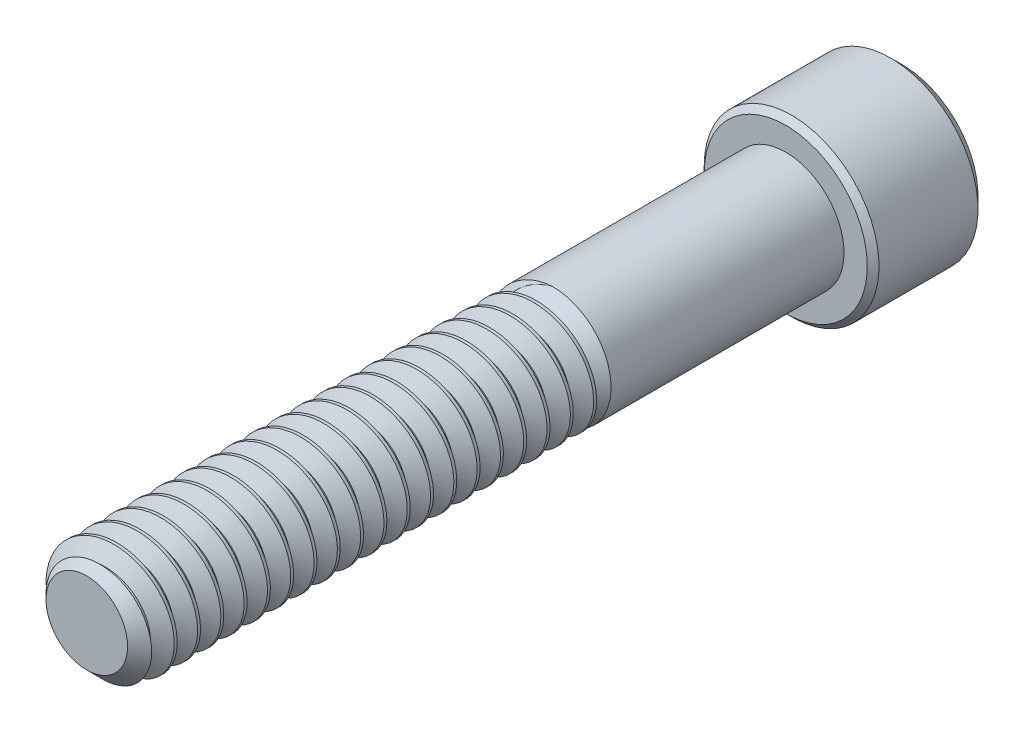
SolidWorks part; units mm, degrees
material "Cast Alloy Steel"
ref_plane "Front Plane" through (0, 0, 0) normal (0, 0, 1) x (1, 0, 0)
ref_plane "Top Plane" through (0, 0, 0) normal (0, 1, 0) x (1, 0, 0)
ref_plane "Right Plane" through (0, 0, 0) normal (1, 0, 0) x (0, 0, -1)
sketch "Sketch1" plane through (0, 0, 0) normal (0, 0, 1) x (1, 0, 0)
  line L0 (0, 3.175) -> (0, -3.175) construction
  circle A0 centre (0, 0) radius 3.175
  dimension "OD" = 6.35
extrude "Extrude1" add sketch "Sketch1" against normal blind 38.1
sketch "Sketch2" plane through (0, 0, 0) normal (0, 0, 1) x (1, 0, 0)
  circle A0 centre (0, 0) radius 3.175 construction
  circle A1 centre (0, 0) radius 3.175
curve "Helix/Spiral1" pitch 1.27 height 27.94 turns 22 parameters "pitch"=1.27
chamfer "Chamfer3" distance 0.9525 angle 45 1 edges at (3.175, 0, 0)
sketch "Sketch3" plane through (0, 0, 0) normal (1, 0, 0) x (0, 0, -1)
  line L0 (-1.1112, 3.175) -> (-0.635, 2.3501)
  line L1 (-0.635, 2.3501) -> (-0.4763, 2.3501)
  line L2 (-0.4763, 2.3501) -> (0, 3.175)
  line L3 (-1.1112, 3.175) -> (0, 3.175)
  line L4 (-0.5556, 3.175) -> (-0.5556, 2.3501) construction
  line L5 (-0.8731, 2.7626) -> (-0.2381, 2.7626) construction
  line L6 (0, 3.175) -> (0, -3.175) construction
  dimension "D1" = 0.1588
  dimension "D2" = 0.635
  dimension "D3" = 60
sweep "Cut-Sweep1" cut profiles "Sketch3" path "Helix/Spiral1"
sketch "Sketch5" plane through (0, 0, 0) normal (1, 0, 0) x (0, 0, -1)
  line L1 (38.1, 3.175) -> (25.4, 3.175)
  line L2 (38.1, 3.175) -> (38.1, 0)
  line L3 (38.1, 0) -> (25.4, 0)
  line L4 (25.4, 3.175) -> (25.4, 0) construction
  line L6 (0, 0) -> (9.9695, 0) construction
  line L8 (25.4, 3.175) -> (22.225, 0)
  line L9 (22.225, 0) -> (25.4, 0)
  line L10 (38.1, -3.175) -> (38.1, 3.175) construction
  dimension "D1" = 45
  dimension "Thread min" = 25.4
revolve "partially thread" add sketch "Sketch5" angle 360 about L6
sketch "Sketch6" plane through (0, 0, -38.1) normal (0, 0, -1) x (-1, 0, 0)
  circle A0 centre (0, 0) radius 4.7625
  dimension "head dia" = 9.525
extrude "Extrude2" add sketch "Sketch6" along normal blind 6.35
sketch "Sketch7" plane through (0, 0, -44.45) normal (0, 0, -1) x (-1, 0, 0)
  line L1 (0, 2.7496) -> (-2.3812, 1.3748)
  line L2 (-2.3812, 1.3748) -> (-2.3813, -1.3748)
  line L3 (-2.3813, -1.3748) -> (0, -2.7496)
  line L4 (0, -2.7496) -> (2.3813, -1.3748)
  line L5 (2.3813, -1.3748) -> (2.3813, 1.3748)
  line L6 (2.3813, 1.3748) -> (0, 2.7496)
  circle A0 centre (0, 0) radius 2.3813 construction
  dimension "hex dia" = 4.7625
extrude "Cut-Extrude1" cut sketch "Sketch7" against normal blind 3.5719
sketch "Sketch8" plane through (0, 0, -44.45) normal (0, 0, -1) x (-1, 0, 0)
  circle A0 centre (0, 0) radius 2.7496
extrude "Cut-Extrude2" cut sketch "Sketch8" against normal blind 0.635 draft 45
chamfer "Chamfer1" distance 0.635 angle 45 1 edges at (-4.7625, 0, -44.45)
chamfer "Chamfer2" distance 0.3175 angle 45 1 edges at (-4.7625, 0, -38.1)
sketch "Sketch9" plane through (0, 0, 0) normal (1, 0, 0) x (0, 0, -1)
  line L0 (0, 3.175) -> (0, -3.175) construction
  line L1 (6.985, 3.175) -> (6.985, -3.175) construction
  line L2 (38.1, 4.7625) -> (38.1, -4.7625) construction
  line L3 (44.45, 4.7625) -> (44.45, -4.7625) construction
  line L4 (44.45, 0) -> (0, 0) construction
  line L5 (61.6852, 3.175) -> (61.6852, -3.175) construction
  dimension "D1" = 6.985
  dimension "D2" = 6.35
  dimension "D3" = 9.525
  dimension "D4" = 38.1
  dimension "Thread Length" = 61.6852
equation "\"D3@Helix/Spiral1\" = \"Thread min@Sketch5\"+(\"pitch@Helix/Spiral1\"*2)"
equation "\"D1@Sketch3\" = \"pitch@Helix/Spiral1\"*.125"
equation "\"D2@Sketch3\" = \"pitch@Helix/Spiral1\"*.5"
equation "\"D1@Cut-Extrude1\" = \"hex dia@Sketch7\"*.75"
equation "\"D1@Chamfer1\" = \"head depth@Extrude2\"/10"
equation "\"D1@Sketch9\" = \"pitch@Helix/Spiral1\"*5.5"
equation "\"D1@Chamfer2\" = \"D1@Chamfer1\"/2"
equation "\"D1@Cut-Extrude2\" = \"D1@Chamfer2\"*2"
equation "\"D1@Chamfer3\" = \"pitch@Helix/Spiral1\"*.750"
equation "\"D2@Sketch9\" = \"head depth@Extrude2\""
equation "\"D3@Sketch9\" = \"head dia@Sketch6\""
equation "\"D4@Sketch9\" = \"screw length@Extrude1\""
